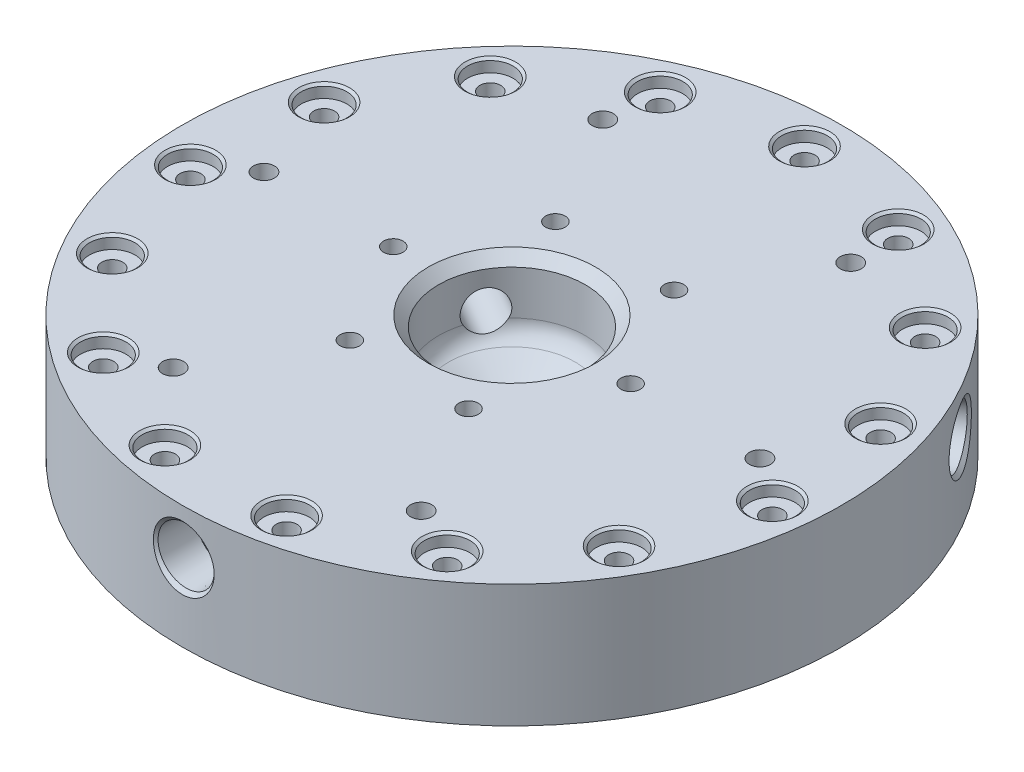
SolidWorks part; units mm, degrees
ref_plane "Front Plane" through (0, 0, 0) normal (0, 0, 1) x (1, 0, 0)
ref_plane "Top Plane" through (0, 0, 0) normal (0, 1, 0) x (1, 0, 0)
ref_plane "Right Plane" through (0, 0, 0) normal (1, 0, 0) x (0, 0, -1)
sketch "Sketch1" plane through (0, 0, 0) normal (0, 1, 0) x (1, 0, 0)
  circle A0 centre (0, 0) radius 80.54
  dimension "D1" = 161.08
extrude "Boss-Extrude1" add sketch "Sketch1" along normal blind 30
sketch "Sketch2" plane through (0, 0, 0) normal (0, 0, 1) x (1, 0, 0)
  line L0 (-6.0682, 0) -> (-6.0682, 4.1132)
  line L1 (-8.5682, 8.4434) -> (-15.4203, 12.3995)
  line L2 (-17.9203, 16.7296) -> (-17.9203, 30)
  line L3 (80.54, 30) -> (-80.54, 30) construction
  line L4 (-17.9203, 30) -> (0, 30)
  line L5 (0, 30) -> (0, 0)
  line L6 (0, 0) -> (-6.0682, 0)
  line L7 (-80.54, 0) -> (80.54, 0) construction
  arc A0 (-15.4203, 12.3995) -> (-17.9203, 16.7296) centre (-12.9203, 16.7296) cw
  arc A1 (-6.0682, 4.1132) -> (-8.5682, 8.4434) centre (-11.0682, 4.1132) ccw
  point P15 (-6.0682, 7)
  dimension "D5" = 5
  dimension "Fuel Outlet Radius" = 6.0682
  dimension "D2" = 7
  dimension "Fuel Chamber Radius" = 17.9203
  dimension "D4" = 30
revolve "Cut-Revolve1" cut sketch "Sketch2" angle 360 about L5
ref_plane "Plane1" through (0, 0, 80.54) normal (0, 0, 1) x (1, 0, 0)
hole_wizard "1/4 NPT Tapped Hole1" positions "Sketch4" profile "Sketch5" size "1/4" standard "ANSI Inch"
sketch "Sketch4" plane through (0, 0, 80.54) normal (0, 0, 1) x (1, 0, 0)
  point P0 (0, 18.9048)
sketch "Sketch5" plane through (0, 18.9048, 80.54) normal (1, 0, 0) x (0, -1, 0)
  line L0 (0, 0) -> (0, 83.3213)
  line L1 (4.6289, 80.54) -> (0, 83.3213)
  line L2 (-4.6289, 80.54) -> (0, 83.3213) construction
  line L3 (4.6289, 80.54) -> (4.6289, 10.02)
  line L4 (4.6289, 10.02) -> (6.5855, 10.02)
  line L5 (6.5855, 10.02) -> (6.858, 0.9208)
  line L6 (6.858, 0.9208) -> (7.7788, 0)
  line L7 (7.7788, 0) -> (0, 0)
  line L8 (0, -6.35) -> (0, 107.95) construction
  line L9 (-6.858, 0.9208) -> (-7.7788, 0) construction
  line L11 (-4.6289, 10.02) -> (-6.5855, 10.02) construction
  line L12 (-6.5855, 10.02) -> (-6.858, 0.9208) construction
  dimension "Tap Drill Dia." = 9.2579
  dimension "Tap Drill Depth" = 80.54
  dimension "Thread Dia." = 13.716
  dimension "Thread Angle" = 3.43
  dimension "Thread Depth" = 10.02
  dimension "C'Sink Dia." = 15.5575
  dimension "C'Sink Angle" = 90
  dimension "Drill Angle" = 118
pattern_circular "CirPattern1" count 3 over 360 about axis through (0, 30, 0) along (0, -1, 0) of "1/4 NPT Tapped Hole1"
hole_wizard "CBORE for #10 Binding Head Machine Screw1" positions "Sketch6" profile "Sketch7" counterbore size "#10" standard "ANSI Inch" end condition through all
sketch "Sketch6" plane through (0, 30, 0) normal (0, 1, 0) x (1, 0, 0)
  point P0 (0, 71.5)
  dimension "D1" = 71.5
sketch "Sketch7" plane through (0, 30, -71.5) normal (1, 0, 0) x (0, 0, 1)
  line L0 (0, 0) -> (0, 30)
  line L1 (0, 30) -> (2.5527, 30)
  line L3 (2.5527, 30) -> (2.5527, 3.1242)
  line L4 (5.5562, 3.1242) -> (2.5527, 3.1242)
  line L5 (5.5562, 3.1242) -> (5.5562, 0.5328)
  line L6 (5.5562, 0.5328) -> (6.1913, 0)
  line L7 (6.1913, 0) -> (0, 0)
  line L8 (-5.5562, 0.5328) -> (-6.1913, 0) construction
  line L11 (0, -6.35) -> (0, 107.95) construction
  dimension "Thru Hole Dia." = 5.1054
  dimension "Thru Hole Depth" = 30
  dimension "C'Bore Dia." = 11.1125
  dimension "C'Bore Depth" = 3.1242
  dimension "Near C'Sink Dia." = 12.3825
  dimension "Near C'Sink Angle" = 100
pattern_circular "CirPattern2" count 15 over 360 about axis through (0, 30, 0) along (0, -1, 0) of "CBORE for #10 Binding Head Machine Screw1"
sketch "Sketch12" plane through (0, 30, 0) normal (0, 1, 0) x (1, 0, 0)
  line L0 (0, 0) -> (0, 60.61)
  line L1 (0, 0) -> (30.305, 52.4898)
  circle A0 centre (0, 0) radius 60.61
  dimension "D1" = 121.22
  dimension "D2" = 30
hole_wizard "13/64 (0.20313) Diameter Hole3" positions "Sketch17" profile "Sketch19" hole size "13/64" standard "ANSI Inch"
sketch "Sketch17" plane through (0, 30, 0) normal (0, 1, 0) x (1, 0, 0)
  point P0 (30.305, 52.4898)
sketch "Sketch19" plane through (30.305, 30, -52.4898) normal (1, 0, 0) x (0, 0, 1)
  line L0 (0, 0) -> (0, 14.2501)
  line L1 (0, 14.2501) -> (2.5798, 12.7)
  line L2 (2.5798, 12.7) -> (2.5798, 0)
  line L5 (2.5798, 0) -> (0, 0)
  line L10 (0, 14.2501) -> (-2.5798, 12.7) construction
  line L11 (0, -6.35) -> (0, 107.95) construction
  dimension "Hole Dia." = 5.1595
  dimension "Hole Depth" = 12.7
  dimension "Drill Angle" = 118
pattern_circular "CirPattern3" count 6 over 360 about axis through (0, 30, 0) along (0, -1, 0) of "13/64 (0.20313) Diameter Hole3" reverse direction yes
sketch "Sketch20" plane through (0, 0, 0) normal (0, -1, 0) x (-1, 0, 0)
  circle A0 centre (0, 0) radius 55.14
  dimension "D1" = 110.28
sketch "Sketch21" plane through (0, 0, 0) normal (0, 0, 1) x (1, 0, 0)
  line L0 (-80.54, 0) -> (80.54, 0) construction
  line L1 (60, 0) -> (65, 0)
  line L2 (60, 0) -> (60, 3)
  line L3 (60, 3) -> (65, 3)
  line L4 (65, 0) -> (65, 3)
  line L5 (0, 0) -> (0, -8.9782) construction
  dimension "D1" = 60
  dimension "D2" = 5
  dimension "D3" = 3
revolve "Cut-Revolve2" cut sketch "Sketch21" angle 360 about L5
chamfer "Chamfer1" distance 2.5 angle 45 1 edges at (-17.9203, 30, 0)
hole_wizard "3/16 (0.1875) Diameter Hole1" positions "Sketch27" profile "Sketch28" hole size "3/16" standard "ANSI Inch"
sketch "Sketch27" plane through (0, 30, 0) normal (0, 1, 0) x (1, 0, 0)
  point P0 (29, 0)
  dimension "D1" = 29
sketch "Sketch28" plane through (29, 30, 0) normal (1, 0, 0) x (0, 0, 1)
  line L0 (0, 0) -> (0, 13.4308)
  line L1 (0, 13.4308) -> (2.3812, 12)
  line L2 (2.3812, 12) -> (2.3812, 0)
  line L5 (2.3812, 0) -> (0, 0)
  line L10 (0, 13.4308) -> (-2.3813, 12) construction
  line L11 (0, -6.35) -> (0, 107.95) construction
  dimension "Hole Dia." = 4.7625
  dimension "Hole Depth" = 12
  dimension "Drill Angle" = 118
pattern_circular "CirPattern4" count 6 over 360 about axis through (0, 30, 0) along (0, -1, 0) of "3/16 (0.1875) Diameter Hole1" reverse direction yes
